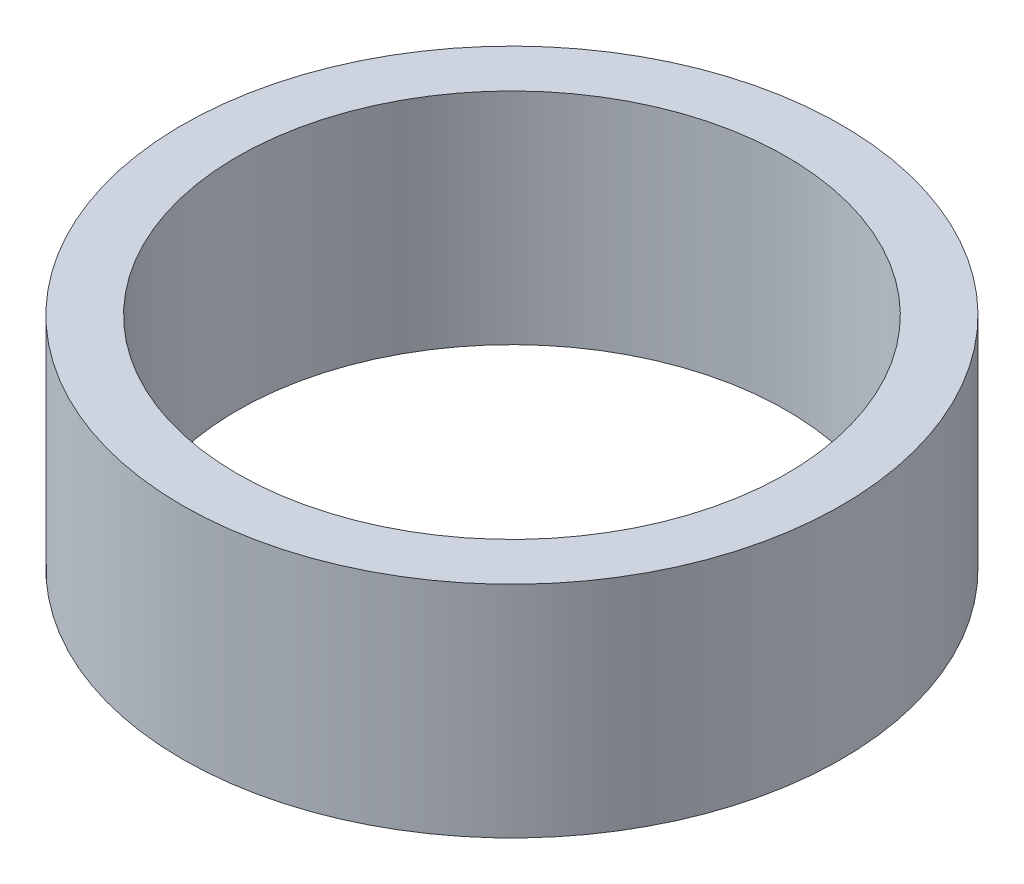
SolidWorks part; units mm, degrees
ref_plane "Front Plane" through (0, 0, 0) normal (0, 0, 1) x (1, 0, 0)
ref_plane "Top Plane" through (0, 0, 0) normal (0, 1, 0) x (1, 0, 0)
ref_plane "Right Plane" through (0, 0, 0) normal (1, 0, 0) x (0, 0, -1)
sketch "Sketch1" plane through (0, 0, 0) normal (0, 1, 0) x (1, 0, 0)
  circle A0 centre (0, 0) radius 45
  dimension "FLANGE_OD" = 90
extrude "Boss-Extrude1" add sketch "Sketch1" along normal blind 30
sketch "Sketch2" plane through (0, 0, 0) normal (0, 1, 0) x (1, 0, 0)
  circle A0 centre (0, 0) radius 37.5
  dimension "BORE_D" = 75
extrude "Cut-Extrude1" cut sketch "Sketch2" along normal through all
sketch "Sketch3" plane through (0, 30, 0) normal (0, 1, 0) x (1, 0, 0)
  circle A0 centre (0, 0) radius 20.3403 construction
  circle A1 centre (-20.3403, 0) radius 1.5
  dimension "BOLT_D" = 3
  dimension "BOLT_PCD" = 40.6807
extrude "Cut-Extrude2" cut sketch "Sketch3" against normal blind 24.1006 rebuild error yes
pattern_circular "CirPattern1" count 8 over 360 rebuild error yes
